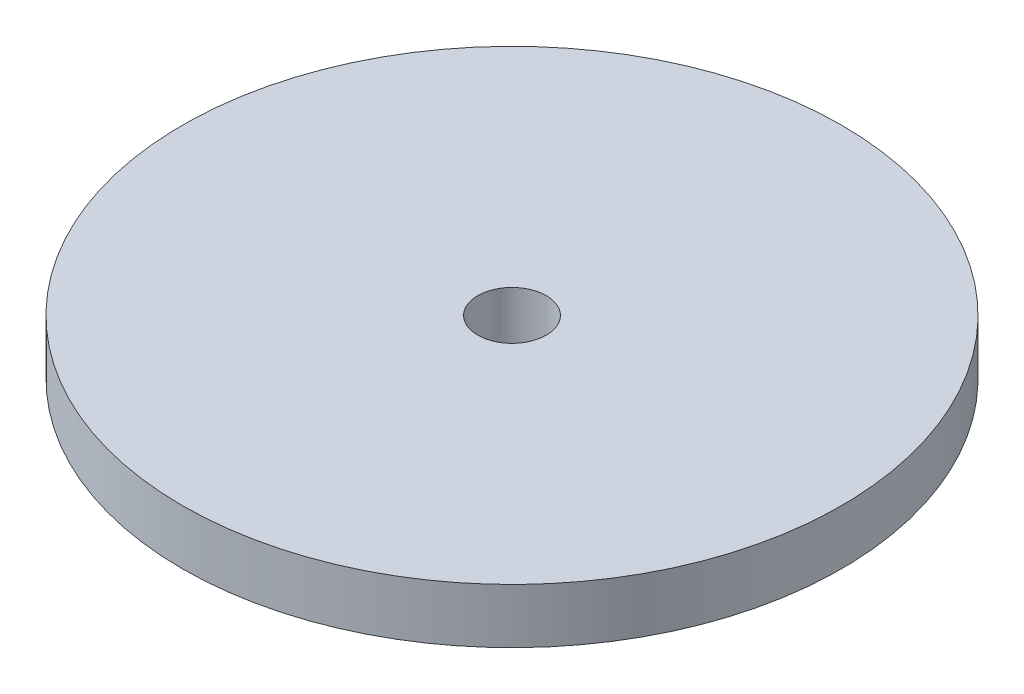
SolidWorks part; units mm, degrees
material "G10 Fiberglass"
ref_plane "Front Plane" through (0, 0, 0) normal (0, 0, 1) x (1, 0, 0)
ref_plane "Top Plane" through (0, 0, 0) normal (0, 1, 0) x (1, 0, 0)
ref_plane "Right Plane" through (0, 0, 0) normal (1, 0, 0) x (0, 0, -1)
sketch "Sketch1" plane through (0, 0, 0) normal (0, 1, 0) x (1, 0, 0)
  circle A0 centre (0, 0) radius 38.227
  dimension "D1" = 76.454
extrude "Boss-Extrude1" add sketch "Sketch1" along normal blind 6.35
sketch "Sketch2" plane through (0, 6.35, 0) normal (0, 1, 0) x (1, 0, 0)
  circle A11 centre (0, 0) radius 3.9751
  dimension "D1" = 7.9502
extrude "Cut-Extrude1" cut sketch "Sketch2" against normal through all contours A11 region at (0, 6.35, 0)
ref_plane "Plane1" through (0, 0, -38.227) normal (0, 0, -1) x (0, -1, 0)
sketch "Sketch4" plane through (0, 0, -38.227) normal (0, 0, -1) x (0, -1, 0)
  circle A0 centre (-4.7625, 0) radius 2.3749
  dimension "D1" = 4.7625
  dimension "D2" = 4.7498
extrude "Cut-Extrude2" [suppressed] cut sketch "Sketch4" against normal blind 6.35
ref_axis "Axis1" through (0, 10.0012, 0) along (0, -1, 0)
pattern_circular "CirPattern1" [suppressed] count 3 over 360 about axis through (0, 10.0012, 0) along (0, -1, 0) of bodies 103
